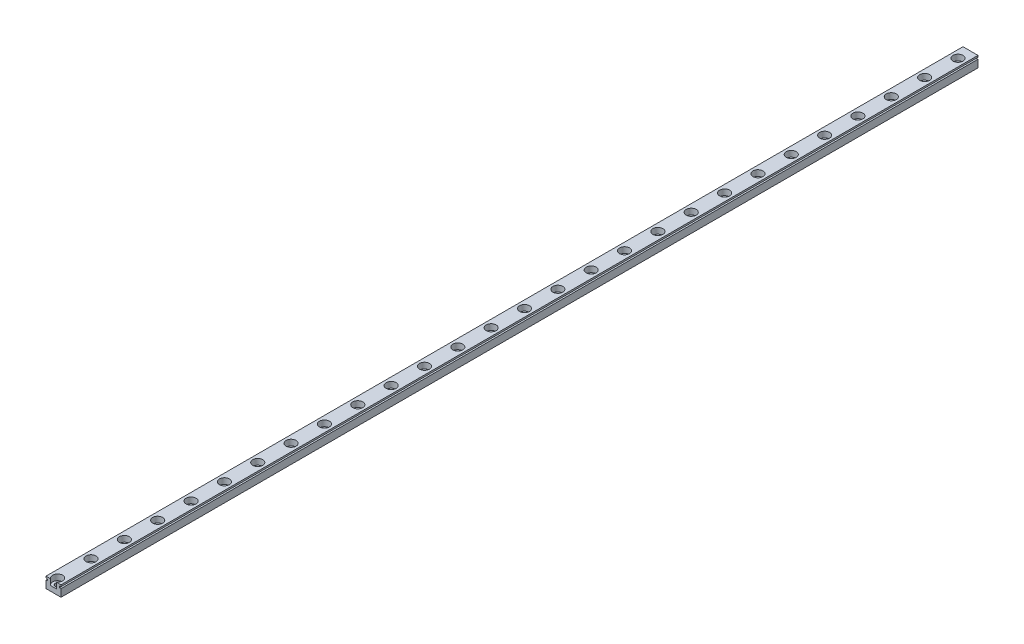
SolidWorks part; units mm, degrees
material "1.0401 (C15)"
ref_plane "前视基准面" through (0, 0, 0) normal (0, 0, 1) x (1, 0, 0)
ref_plane "上视基准面" through (0, 0, 0) normal (0, 1, 0) x (1, 0, 0)
ref_plane "右视基准面" through (0, 0, 0) normal (1, 0, 0) x (0, 0, -1)
sketch "草图1" plane through (0, 0, 0) normal (0, 0, 1) x (1, 0, 0)
  line L0 (0, -0.8589) -> (0, 7.8911) construction
  line L1 (-4.5, 0) -> (4.5, 0)
  line L2 (4.5, 0) -> (4.5, 4.5)
  line L3 (4.5, 5.5) -> (3.5, 5.5)
  line L4 (3.5, 5.5) -> (3.5, 4.5)
  line L5 (4.5, 5.5) -> (4.5, 6.5)
  line L6 (4.5, 6.5) -> (-4.5, 6.5)
  line L7 (3.5, 4.5) -> (4.5, 4.5)
  line L8 (-4.5, 0) -> (-4.5, 4.5)
  line L9 (-3.5, 4.5) -> (-4.5, 4.5)
  line L10 (-3.5, 5.5) -> (-3.5, 4.5)
  line L11 (-4.5, 5.5) -> (-3.5, 5.5)
  line L12 (-4.5, 5.5) -> (-4.5, 6.5)
  point P12 (0, 0)
  point P17 (0, 6.5)
  dimension "D1" = 4.5
  dimension "D2" = 6.5
  dimension "D3" = 1
  dimension "D4" = 1
  dimension "D5" = 1
  dimension "D6" = 4.5
extrude "凸台-拉伸1" add sketch "草图1" along normal blind 550
sketch "草图2" plane through (0, 0, 0) normal (1, 0, 0) x (0, 0, -1)
  line L0 (-7.5, 7.6159) -> (-7.5, -2.728) construction
  line L1 (-7.5, 0) -> (-6, 0)
  line L2 (-550, 0) -> (0, 0) construction
  line L3 (-6, 0) -> (-6, 3)
  line L4 (-6, 3) -> (-4.5, 3)
  line L5 (-4.5, 3) -> (-4.5, 6.5)
  line L6 (-550, 6.5) -> (0, 6.5) construction
  line L7 (-4.5, 6.5) -> (-7.5, 6.5)
  line L8 (-7.5, 0) -> (-7.5, 6.5)
  dimension "D1" = 7.5
  dimension "D2" = 1.5
  dimension "D3" = 3
  dimension "D4" = 3.5
revolve "切除-旋转1" cut sketch "草图2" angle 360 about L0
pattern_linear "阵列(线性)1" count 28 spacing 20 along (0, 0, 1) of "切除-旋转1"
